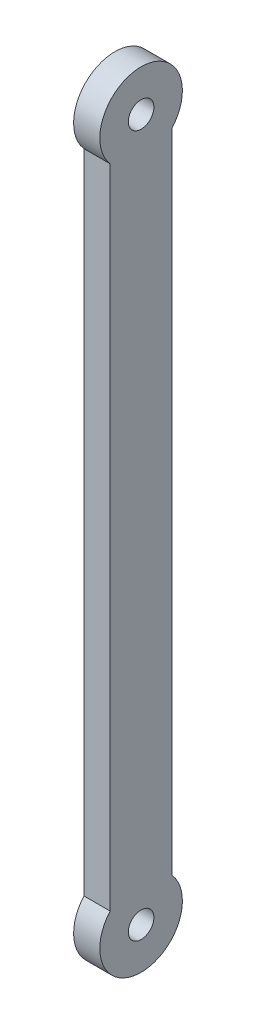
SolidWorks part; units mm, degrees
ref_plane "Front Plane" through (0, 0, 0) normal (0, 0, 1) x (1, 0, 0)
ref_plane "Top Plane" through (0, 0, 0) normal (0, 1, 0) x (1, 0, 0)
ref_plane "Right Plane" through (0, 0, 0) normal (1, 0, 0) x (0, 0, -1)
sketch "Sketch1" plane through (0, 0, 0) normal (1, 0, 0) x (0, 0, -1)
  line L0 (0, 0) -> (-3.75, -3.3072) construction
  line L2 (3.75, -3.3072) -> (3.75, -81.6928)
  line L3 (3.75, -81.6928) -> (-3.75, -81.6928) construction
  line L4 (-3.75, -3.3072) -> (-3.75, -81.6928)
  line L5 (3.75, -3.3072) -> (-3.75, -3.3072) construction
  line L6 (0, 0) -> (3.75, -3.3072) construction
  circle A0 centre (0, 0) radius 1.55
  arc A1 (3.75, -3.3072) -> (-3.75, -3.3072) centre (0, 0) ccw
  arc A2 (-3.75, -81.6928) -> (3.75, -81.6928) centre (0, -85) ccw
  circle A3 centre (0, -85) radius 1.55
  dimension "D1" = 3.1
  dimension "D2" = 10
  dimension "D4" = 10
  dimension "D6" = 3.1
  dimension "D3" = 7.5
  dimension "D5" = 85
extrude "Boss-Extrude3" add sketch "Sketch1" along normal blind 3.175
